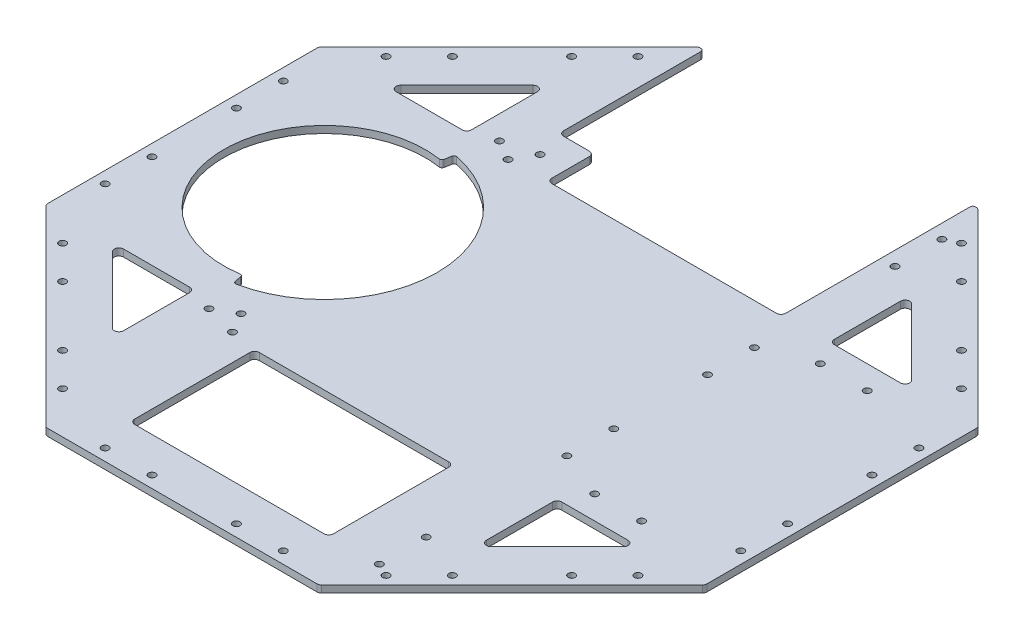
SolidWorks part; units mm, degrees
ref_plane "前视基准面" through (0, 0, 0) normal (0, 0, 1) x (1, 0, 0)
ref_plane "上视基准面" through (0, 0, 0) normal (0, 1, 0) x (1, 0, 0)
ref_plane "右视基准面" through (0, 0, 0) normal (1, 0, 0) x (0, 0, -1)
other "Configuration Table"
sketch "草图1" plane through (0, 0, 0) normal (0, 1, 0) x (1, 0, 0)
  line L0 (-138.5819, -57.4025) -> (-57.4025, -138.5819) construction
  line L2 (-138.5819, 57.4025) -> (-138.5819, -57.4025) construction
  line L3 (-57.4025, -57.4025) -> (57.4025, -57.4025)
  line L4 (138.5819, 57.4025) -> (138.5819, -57.4025) construction
  line L5 (-138.5819, 57.4025) -> (138.5819, -57.4025) construction
  line L6 (-138.5819, -57.4025) -> (138.5819, 57.4025) construction
  line L7 (-57.4025, -138.5819) -> (57.4025, -138.5819) construction
  line L8 (57.4025, -138.5819) -> (138.5819, -57.4025) construction
  line L9 (0, 0) -> (0, -138.5819) construction
  line L10 (-57.4025, -138.5819) -> (-57.4025, -57.4025)
  line L11 (57.4025, -138.5819) -> (57.4025, -57.4025)
  line L12 (57.4025, -57.4025) -> (138.5819, -57.4025) construction
  line L13 (0, 0) -> (138.5819, 0) construction
  line L14 (57.4025, 138.5819) -> (138.5819, 57.4025) construction
  line L15 (57.4025, 138.5819) -> (57.4025, 57.4025)
  line L16 (-57.4025, 57.4025) -> (57.4025, 57.4025)
  line L17 (-57.4025, 138.5819) -> (-57.4025, 57.4025)
  line L18 (-138.5819, 57.4025) -> (-57.4025, 138.5819) construction
  line L19 (-140.5819, -58.2309) -> (-58.8167, -139.9961)
  line L20 (-140.5819, 58.2309) -> (-140.5819, -58.2309)
  line L21 (-140.5819, 58.2309) -> (-58.8167, 139.9961)
  line L22 (58.8167, 139.9961) -> (140.5819, 58.2309)
  line L23 (140.5819, 58.2309) -> (140.5819, -58.2309)
  line L24 (58.8167, -139.9961) -> (140.5819, -58.2309)
  line L25 (-58.8167, -139.9961) -> (-57.4025, -138.5819)
  line L26 (57.4025, -138.5819) -> (58.8167, -139.9961)
  line L27 (57.4025, 138.5819) -> (58.8167, 139.9961)
  line L28 (-58.8167, 139.9961) -> (-57.4025, 138.5819)
  point P0 (0, 0)
  dimension "D1" = 300
  dimension "D2" = 135
  dimension "D3" = 2
extrude "凸台-拉伸1" add sketch "草图1" along normal blind 3
sketch "草图6" plane through (0, 3, 0) normal (0, 1, 0) x (1, 0, 0)
  line L6 (0, 0) -> (-140.5819, 0) construction
  line L7 (-140.5819, 58.2309) -> (-140.5819, -58.2309) construction
  line L8 (-57.4025, 57.4025) -> (-42.4025, 57.4025)
  line L9 (-42.4025, 77.4025) -> (-42.4025, 57.4025)
  line L10 (-57.4025, 77.4025) -> (-42.4025, 77.4025)
  line L11 (-57.4025, 77.4025) -> (-57.4025, 57.4025)
  line L12 (57.4025, 57.4025) -> (-57.4025, 57.4025) construction
  line L13 (-57.4025, 57.4025) -> (-57.4025, 138.5819) construction
  line L14 (-58.8167, -139.9961) -> (-58.2309, -140.5819)
  line L19 (-58.2309, -140.5819) -> (58.2309, -140.5819)
  line L20 (58.8167, -139.9961) -> (58.2309, -140.5819)
  line L21 (-58.8167, -139.9961) -> (-57.4025, -138.5819) construction
  line L22 (-57.4025, -138.5819) -> (-57.4025, -57.4025) construction
  line L23 (-57.4025, -57.4025) -> (57.4025, -57.4025) construction
  line L24 (57.4025, -57.4025) -> (57.4025, -138.5819) construction
  line L25 (57.4025, -138.5819) -> (58.8167, -139.9961) construction
  line L26 (-58.8167, -139.9961) -> (-57.4025, -138.5819)
  line L27 (-57.4025, -138.5819) -> (-57.4025, -57.4025)
  line L28 (-57.4025, -57.4025) -> (57.4025, -57.4025)
  line L29 (57.4025, -57.4025) -> (57.4025, -138.5819)
  line L30 (57.4025, -138.5819) -> (58.8167, -139.9961)
  line L31 (0, -140.5819) -> (0, 0) construction
  line L32 (58.8167, -139.9961) -> (140.5819, -58.2309) construction
  line L34 (-42.4025, -67.4025) -> (42.4025, -67.4025)
  line L35 (-42.4025, -67.4025) -> (-42.4025, -120.5819)
  line L36 (-42.4025, -120.5819) -> (42.4025, -120.5819)
  line L37 (42.4025, -67.4025) -> (42.4025, -120.5819)
  line L38 (-42.4025, -67.4025) -> (42.4025, -120.5819) construction
  line L39 (-42.4025, -120.5819) -> (42.4025, -67.4025) construction
  point P31 (0, -93.9922)
  dimension "D1" = 20
  dimension "D2" = 15
  dimension "D3" = 20
  dimension "D4" = 10
  dimension "D5" = 15
extrude "凸台-拉伸2" add sketch "草图6" against normal up to surface (3 mm away) up to face at (0, 0, 0)
sketch "草图2" plane through (0, 3, 0) normal (0, 1, 0) x (1, 0, 0)
  line L0 (-135.5819, 18) -> (-135.5819, -18) construction
  line L1 (0, 0) -> (-135.5819, 0) construction
  line L2 (-83.143, 108.5988) -> (-108.5988, 83.143) construction
  line L3 (-135.5819, 18) -> (-135.5819, 38) construction
  line L4 (0, 0) -> (0, 57.4025) construction
  line L5 (-83.143, 108.5988) -> (-69.0008, 122.741) construction
  line L6 (135.5819, 18) -> (135.5819, 38) construction
  line L7 (135.5819, 18) -> (135.5819, -18) construction
  line L9 (-140.5819, 58.2309) -> (-140.5819, -58.2309) construction
  line L10 (108.5988, -83.143) -> (122.741, -69.0008) construction
  line L11 (108.5988, -83.143) -> (83.143, -108.5988) construction
  line L12 (18, 135.5819) -> (-18, 135.5819) construction
  line L13 (18, 135.5819) -> (38, 135.5819) construction
  line L14 (18, -135.5819) -> (38, -135.5819) construction
  line L15 (18, -135.5819) -> (-18, -135.5819) construction
  line L16 (108.5988, 83.143) -> (83.143, 108.5988) construction
  line L17 (108.5988, 83.143) -> (122.741, 69.0008) construction
  line L18 (-83.143, -108.5988) -> (-69.0008, -122.741) construction
  line L19 (-83.143, -108.5988) -> (-108.5988, -83.143) construction
  line L20 (-95.8709, 95.8709) -> (0, 0) construction
  line L21 (57.4025, 57.4025) -> (-42.4025, 57.4025) construction
  circle A0 centre (-135.5819, 18) radius 1.5
  circle A2 centre (-135.5819, 38) radius 1.5
  circle A3 centre (-135.5819, -18) radius 1.5
  circle A4 centre (-135.5819, -38) radius 1.5
  circle A5 centre (135.5819, -38) radius 1.5
  circle A6 centre (135.5819, -18) radius 1.5
  circle A7 centre (135.5819, 38) radius 1.5
  circle A8 centre (135.5819, 18) radius 1.5
  circle A9 centre (-83.143, 108.5988) radius 1.5
  circle A10 centre (-69.0008, 122.741) radius 1.5
  circle A11 centre (-108.5988, 83.143) radius 1.5
  circle A12 centre (-122.741, 69.0008) radius 1.5
  circle A13 centre (69.0008, -122.741) radius 1.5
  circle A14 centre (83.143, -108.5988) radius 1.5
  circle A15 centre (122.741, -69.0008) radius 1.5
  circle A16 centre (108.5988, -83.143) radius 1.5
  circle A17 centre (18, 135.5819) radius 1.5
  circle A18 centre (38, 135.5819) radius 1.5
  circle A19 centre (-18, 135.5819) radius 1.5
  circle A20 centre (-38, 135.5819) radius 1.5
  circle A21 centre (-38, -135.5819) radius 1.5
  circle A22 centre (-18, -135.5819) radius 1.5
  circle A23 centre (38, -135.5819) radius 1.5
  circle A24 centre (18, -135.5819) radius 1.5
  circle A25 centre (108.5988, 83.143) radius 1.5
  circle A26 centre (122.741, 69.0008) radius 1.5
  circle A27 centre (83.143, 108.5988) radius 1.5
  circle A28 centre (69.0008, 122.741) radius 1.5
  circle A29 centre (-122.741, -69.0008) radius 1.5
  circle A30 centre (-108.5988, -83.143) radius 1.5
  circle A31 centre (-69.0008, -122.741) radius 1.5
  circle A32 centre (-83.143, -108.5988) radius 1.5
  point P74 (0, 0)
  dimension "D2" = 3
  dimension "D1" = 36
  dimension "D3" = 5
  dimension "D4" = 20
  dimension "D6" = 45
  dimension "D5" = 4
extrude "切除-拉伸1" cut sketch "草图2" against normal blind 10
sketch "草图3" plane through (0, 3, 0) normal (0, 1, 0) x (1, 0, 0)
  line L0 (0, 0) -> (-80, 0) construction
  circle A0 centre (-80, 0) radius 43
  dimension "D2" = 86
  dimension "D1" = 80
extrude "切除-拉伸2" cut sketch "草图3" against normal blind 10
sketch "草图4" plane through (0, 3, 0) normal (0, 1, 0) x (1, 0, 0)
  line L0 (-80, 0) -> (-50, -51.9615) construction
  line L1 (-80, 0) -> (0, 0) construction
  line L2 (-54.3301, -54.4615) -> (-45.6699, -49.4615) construction
  line L3 (-54.3301, -54.4615) -> (-84.3301, -2.5) construction
  line L4 (-80, 0) -> (-84.3301, -2.5) construction
  line L5 (-54.3301, -54.4615) -> (-58.6603, -56.9615) construction
  line L6 (-58.6603, -56.9615) -> (-67.3205, -61.9615) construction
  line L7 (-58.6603, -56.9615) -> (-53.6603, -65.6218) construction
  circle A0 centre (-80, 0) radius 60 construction
  circle A12 centre (-58.6603, -56.9615) radius 1.5
  circle A13 centre (-67.3205, -61.9615) radius 1.5
  circle A14 centre (-53.6603, -65.6218) radius 1.5
  circle A15 centre (-53.6603, 65.6218) radius 1.5
  circle A16 centre (-58.6603, 56.9615) radius 1.5
  circle A17 centre (-67.3205, 61.9615) radius 1.5
  point P3 (-50, -51.9615)
  dimension "D1" = 60
  dimension "D3" = 10
  dimension "D4" = 5
  dimension "D5" = 3
  dimension "D6" = 10
  dimension "D2" = 60
  dimension "D7" = 10
extrude "切除-拉伸3" cut sketch "草图4" against normal blind 10
sketch "草图7" plane through (0, 3, 0) normal (0, 1, 0) x (1, 0, 0)
  line L0 (0, 0) -> (140.5819, 0) construction
  line L1 (140.5819, -58.2309) -> (140.5819, 58.2309) construction
  line L2 (63.4025, 120) -> (63.4025, 100) construction
  line L3 (63.4025, 40) -> (63.4025, 20) construction
  line L4 (57.4025, 138.5819) -> (57.4025, 57.4025) construction
  line L5 (63.4025, -40) -> (63.4025, -20) construction
  line L6 (63.4025, -120) -> (63.4025, -100) construction
  circle A0 centre (63.4025, 120) radius 1.5
  circle A1 centre (63.4025, 100) radius 1.5
  circle A2 centre (63.4025, 40) radius 1.5
  circle A3 centre (63.4025, 20) radius 1.5
  circle A4 centre (63.4025, -20) radius 1.5
  circle A5 centre (63.4025, -40) radius 1.5
  circle A6 centre (63.4025, -100) radius 1.5
  circle A7 centre (63.4025, -120) radius 1.5
  dimension "D6" = 3
  dimension "D1" = 20
  dimension "D2" = 20
  dimension "D3" = 20
  dimension "D4" = 60
  dimension "D5" = 6
extrude "切除-拉伸4" cut sketch "草图7" against normal blind 10
sketch "草图8" plane through (0, 3, 0) normal (0, 1, 0) x (1, 0, 0)
  line L0 (0, 0) -> (140.5819, 0) construction
  line L1 (140.5819, -58.2309) -> (140.5819, 58.2309) construction
  line L2 (0, 0) -> (0, -140.5819) construction
  line L16 (77.4025, -58.1261) -> (77.4025, -93.1261)
  line L17 (77.4025, -93.1261) -> (112.4025, -58.1261)
  line L18 (112.4025, -58.1261) -> (77.4025, -58.1261)
  line L20 (58.2309, -140.5819) -> (140.5819, -58.2309) construction
  line L21 (77.4025, -58.1261) -> (94.9025, -75.6261) construction
  line L22 (-77.4025, -93.1261) -> (-112.4025, -58.1261)
  line L23 (-77.4025, -58.1261) -> (-77.4025, -93.1261)
  line L24 (-112.4025, -58.1261) -> (-77.4025, -58.1261)
  line L25 (77.4025, 93.1261) -> (112.4025, 58.1261)
  line L26 (77.4025, 58.1261) -> (77.4025, 93.1261)
  line L27 (112.4025, 58.1261) -> (77.4025, 58.1261)
  line L28 (-77.4025, 58.1261) -> (-77.4025, 93.1261)
  line L29 (-112.4025, 58.1261) -> (-77.4025, 58.1261)
  line L30 (-77.4025, 93.1261) -> (-112.4025, 58.1261)
  line L32 (57.4025, 138.5819) -> (57.4025, 57.4025) construction
  line L33 (-58.2309, -140.5819) -> (58.2309, -140.5819) construction
  dimension "D1" = 20
  dimension "D2" = 20
  dimension "D3" = 35
extrude "切除-拉伸5" cut sketch "草图8" against normal blind 10
sketch "草图9" plane through (0, 3, 0) normal (0, 1, 0) x (1, 0, 0)
  line L0 (83.4025, -48.1261) -> (103.4025, -48.1261) construction
  line L1 (112.4025, -58.1261) -> (77.4025, -58.1261) construction
  line L2 (0, 0) -> (140.5819, 0) construction
  line L3 (140.5819, -58.2309) -> (140.5819, 58.2309) construction
  circle A0 centre (83.4025, -48.1261) radius 1.5
  circle A1 centre (103.4025, -48.1261) radius 1.5
  circle A2 centre (63.4025, -40) radius 1.5 construction
  circle A3 centre (103.4025, 48.1261) radius 1.5
  circle A4 centre (83.4025, 48.1261) radius 1.5
  dimension "D2" = 3
  dimension "D1" = 20
  dimension "D3" = 10
  dimension "D4" = 20
extrude "切除-拉伸6" cut sketch "草图9" against normal blind 10
fillet "圆角1" radius 2 30 edges at (-42.4025, 1.5, 67.4025) (-42.4025, 1.5, 120.5819) (42.4025, 1.5, 120.5819) (42.4025, 1.5, 67.4025) (-58.2309, 1.5, 140.5819) (-140.5819, 1.5, 58.2309) (-140.5819, 1.5, -58.2309) (-58.8167, 1.5, -139.9961) (-57.4025, 1.5, -138.5819) (-57.4025, 1.5, -77.4025) (-42.4025, 1.5, -77.4025) (-42.4025, 1.5, -57.4025) (57.4025, 1.5, -57.4025) (57.4025, 1.5, -138.5819) (58.8167, 1.5, -139.9961) (140.5819, 1.5, -58.2309) (58.2309, 1.5, 140.5819) (77.4025, 1.5, 58.1261) (77.4025, 1.5, 93.1261) (112.4025, 1.5, 58.1261) (-77.4025, 1.5, -58.1261) (-77.4025, 1.5, -93.1261) (-112.4025, 1.5, -58.1261) (77.4025, 1.5, -58.1261) (112.4025, 1.5, -58.1261) (77.4025, 1.5, -93.1261) (-77.4025, 1.5, 58.1261) (-112.4025, 1.5, 58.1261) (-77.4025, 1.5, 93.1261) (140.5819, 1.5, 58.2309)
sketch "草图10" plane through (0, 3, 0) normal (0, 1, 0) x (1, 0, 0)
  line L0 (-80, 0) -> (0, 0) construction
  line L1 (-71.6649, 47.2708) -> (-80, 0)
  line L2 (-80, 0) -> (-71.6649, -47.2708)
  arc A0 (-71.6649, -47.2708) -> (-71.6649, 47.2708) centre (-80, 0) ccw
  circle A1 centre (-80, 0) radius 43 construction
  dimension "D1" = 5
  dimension "D2" = 80
  dimension "D3" = 80
extrude "走线槽" cut sketch "草图10" against normal blind 10
fillet "圆角2" radius 1 4 edges at (-71.6649, 1.5, -47.2708) (-71.6649, 1.5, 47.2708) (-72.5331, 1.5, 42.3467) (-72.5331, 1.5, -42.3467)
